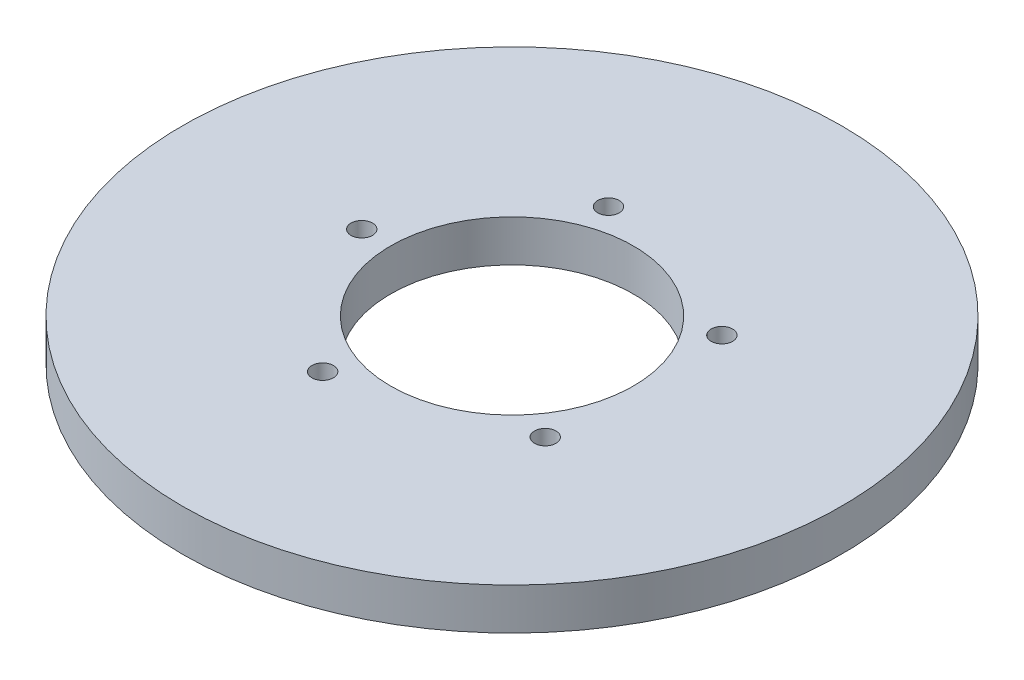
SolidWorks part; units mm, degrees
ref_plane "Front Plane" through (0, 0, 0) normal (0, 0, 1) x (1, 0, 0)
ref_plane "Top Plane" through (0, 0, 0) normal (0, 1, 0) x (1, 0, 0)
ref_plane "Right Plane" through (0, 0, 0) normal (1, 0, 0) x (0, 0, -1)
sketch "Sketch1" plane through (0, 0, 0) normal (0, 1, 0) x (1, 0, 0)
  circle A0 centre (0, 0) radius 95
  dimension "FLANGE_OD" = 190
extrude "Boss-Extrude1" add sketch "Sketch1" along normal blind 12
sketch "Sketch2" plane through (0, 0, 0) normal (0, 1, 0) x (1, 0, 0)
  circle A0 centre (0, 0) radius 35
  dimension "BORE_D" = 70
extrude "Cut-Extrude1" cut sketch "Sketch2" along normal through all
sketch "Sketch3" plane through (0, 12, 0) normal (0, 1, 0) x (1, 0, 0)
  circle A0 centre (0, 0) radius 43.3131 construction
  circle A1 centre (-43.3131, 0) radius 3.098
  dimension "BOLT_D" = 6.196
  dimension "BOLT_PCD" = 86.6263
extrude "Cut-Extrude2" cut sketch "Sketch3" against normal blind 11.7717
pattern_circular "CirPattern1" count 5 over 360 about axis through (0, 0, 0) along (0, 1, 0) of "Cut-Extrude2"
